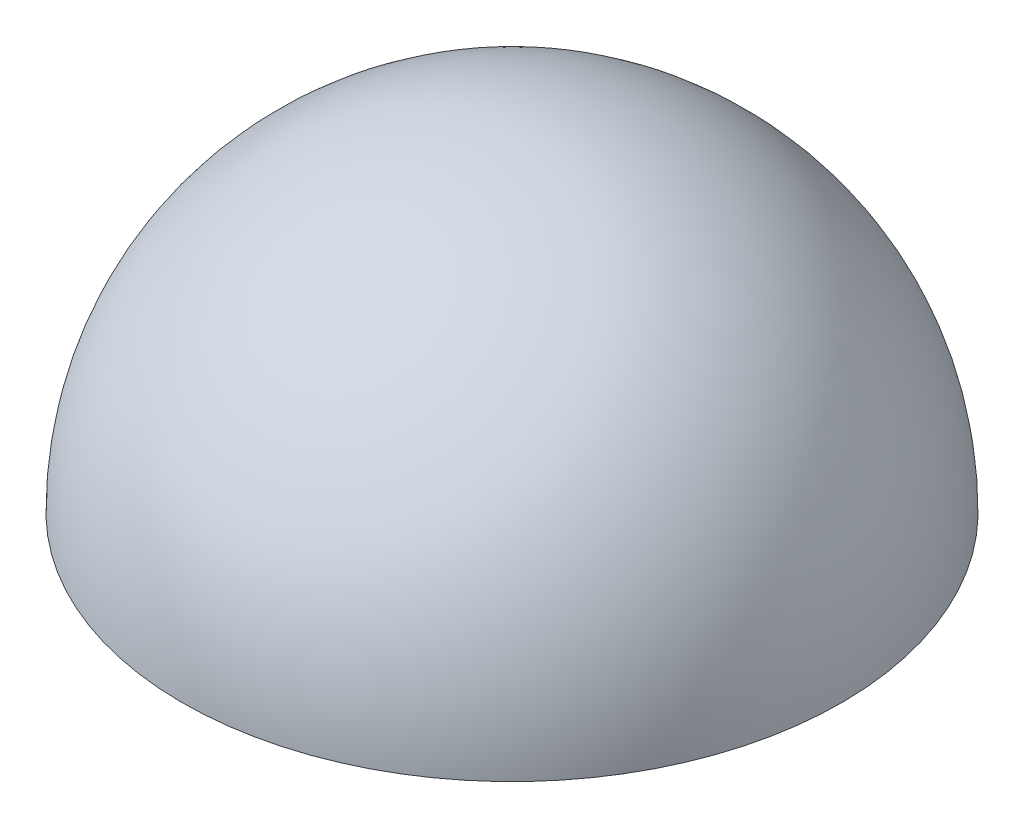
SolidWorks part; units mm, degrees
ref_plane "Front Plane" through (0, 0, 0) normal (0, 0, 1) x (1, 0, 0)
ref_plane "Top Plane" through (0, 0, 0) normal (0, 1, 0) x (1, 0, 0)
ref_plane "Right Plane" through (0, 0, 0) normal (1, 0, 0) x (0, 0, -1)
sketch "Sketch1" plane through (0, 0, 0) normal (0, 1, 0) x (1, 0, 0)
  line L0 (-33.5889, 83.619) -> (-24.0764, -62.1209)
  circle A0 centre (-28.8326, 10.749) radius 73.025
  dimension "D1" = 146.05
revolve "Revolve1" add sketch "Sketch1" angle 180 about L0 region at (-59.7596, 0, -8.7304) reverse direction yes
